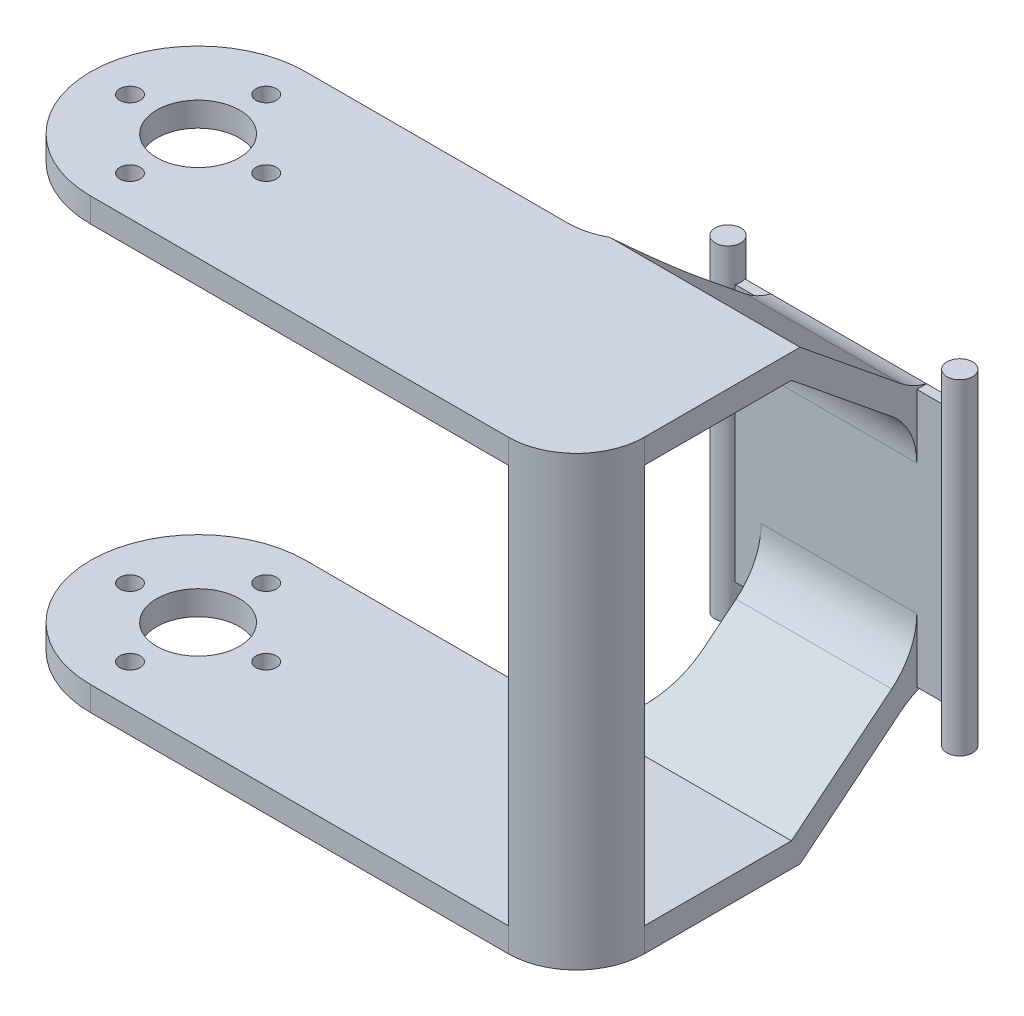
SolidWorks part; units mm, degrees
ref_plane "Front Plane" through (0, 0, 0) normal (0, 0, 1) x (1, 0, 0)
ref_plane "Top Plane" through (0, 0, 0) normal (0, 1, 0) x (1, 0, 0)
ref_plane "Right Plane" through (0, 0, 0) normal (1, 0, 0) x (0, 0, -1)
sketch "Sketch1" plane through (0, 0, 0) normal (0, 1, 0) x (1, 0, 0)
  line L1 (11.915, 0.5) -> (-11.915, 0.5)
  line L2 (11.915, 0.5) -> (11.915, -0.5)
  line L3 (11.915, -0.5) -> (-11.915, -0.5)
  line L4 (-11.915, 0.5) -> (-11.915, -0.5)
  line L5 (11.915, 0.5) -> (-11.915, -0.5) construction
  line L6 (11.915, -0.5) -> (-11.915, 0.5) construction
  point P0 (0, 0)
  dimension "D1" = 23.83
  dimension "D3" = 1
extrude "Boss-Extrude1" add sketch "Sketch1" along normal blind 26.5
ref_plane "Plane1" through (0, 13.25, 0) normal (0, 1, 0) x (1, 0, 0)
sketch "Sketch2" plane through (0, 13.25, 0) normal (0, 1, 0) x (1, 0, 0)
  line L0 (11.915, -0.5) -> (11.915, 0.5) construction
  line L1 (-11.915, 0.5) -> (-11.915, -0.5) construction
  line L2 (11.915, -0.5) -> (11.915, 0.5) construction
  line L3 (-11.915, 0.5) -> (-11.915, -0.5) construction
  circle A0 centre (-11.915, 0) radius 1.325
  circle A1 centre (11.915, 0) radius 1.325
  dimension "D1" = 2.65
extrude "Boss-Extrude2" add sketch "Sketch2" along normal mid plane 33.5
sketch "Sketch3" plane through (0, 26.5, 0) normal (0, 1, 0) x (1, 0, 0)
  line L0 (-10.688, -0.5) -> (10.688, -0.5) construction
  line L1 (-7.5, -0.5) -> (7.5, -0.5)
  line L2 (-7.5, -0.5) -> (-7.5, -26.5)
  line L3 (-7.5, -26.5) -> (7.5, -26.5)
  line L4 (7.5, -0.5) -> (7.5, -26.5)
  line L5 (0, -1000) -> (0, 49000) construction
  line L6 (-7.5, -26.5) -> (-32.5, -26.5)
  line L7 (-7.5, -26.5) -> (-7.5, -3.5)
  line L8 (-7.5, -3.5) -> (-32.5, -3.5)
  line L9 (-32.5, -26.5) -> (-32.5, -3.5)
  line L11 (-4.5, -3.5) -> (4.5, -3.5)
  line L12 (4.5, -3.5) -> (4.5, -23.5)
  line L13 (-4.5, -23.5) -> (4.5, -23.5)
  line L14 (-10.5, -23.5) -> (-29.5, -23.5)
  line L16 (-10.5, -6.5) -> (-29.5, -6.5)
  line L18 (-29.5, -23.5) -> (-29.5, -6.5) construction
  line L19 (-10.5, -23.5) -> (-10.5, -6.5) construction
  line L20 (-4.5, -3.5) -> (-4.5, -23.5) construction
  line L21 (-4.5, -3.5) -> (-4.5, -6.5)
  line L22 (-4.5, -6.5) -> (-10.5, -6.5)
  line L23 (-4.5, -23.5) -> (-10.5, -23.5)
  line L24 (-18.5, -6.5) -> (-18.5, -23.5)
  circle A0 centre (-32.5, -15) radius 11.5
  circle A1 centre (-32.5, -15) radius 4.25
  circle A2 centre (-32.5, -15) radius 7 construction
  circle A3 centre (-32.5, -8) radius 1.05
  circle A4 centre (-25.5, -15) radius 1.05
  circle A5 centre (-32.5, -22) radius 1.05
  circle A6 centre (-39.5, -15) radius 1.05
  point P10 (0, -0.5)
  line M14 (-10.688, -0.5) -> (10.688, -0.5)
  dimension "D5" = 8.5
  dimension "D6" = 14
  dimension "D7" = 2.1
  dimension "D1" = 15
  dimension "D2" = 26
  dimension "D3" = 23
  dimension "D4" = 25
  dimension "D9" = 14
  dimension "D8" = 3
extrude "Boss-Extrude3" [suppressed] add sketch "Sketch3" against normal up to surface (18.5 mm away) contours L4 L2 L3 M14 | A0 L6 L2 L8 | A5 L9 A0 A3 A1 A4 | A5 L9 A1 A3 A0 A6 | A0 L16 L22 L2 L8 | A0 L6 L2 L23 L14
sketch "Sketch4" plane through (0, 0, 0) normal (1, 0, 0) x (0, 0, -1)
  line L0 (-0.5, 26.5) -> (-12.5, 36.25)
  line L1 (-12.5, 36.25) -> (-35.5, 36.25)
  line L2 (-35.5, 36.25) -> (-35.5, 33.75)
  line L3 (-35.5, 33.75) -> (-13.3876, 33.75)
  line L4 (-13.3876, 33.75) -> (-0.5, 23.2788)
  line L5 (-0.5, 26.5) -> (-0.5, 0) construction
  line L6 (-0.5, 26.5) -> (-0.5, 0)
  line L7 (-0.5, 0) -> (-12.5, -9.75)
  line L8 (-12.5, -9.75) -> (-35.5, -9.75)
  line L9 (-35.5, -9.75) -> (-35.5, -7.25)
  line L10 (-35.5, -7.25) -> (-13.3876, -7.25)
  line L11 (-13.3876, -7.25) -> (-0.5, 3.2212)
  line L12 (-1000.5, 13.25) -> (48999.5, 13.25) construction
  line L13 (-35.5, 33.75) -> (-35.5, -7.25) construction
  point P3 (-35.5, 13.25)
  point P20 (-0.5, 13.25)
  dimension "D1" = 2.5
  dimension "D2" = 41
  dimension "D3" = 23
  dimension "D4" = 2.5
  dimension "D5" = 35
  dimension "D6" = 2.5
extrude "Boss-Extrude4" add sketch "Sketch4" along normal mid plane 16 contours L6 L0 L1 L2 L3 L4 | L11 L10 L9 L8 L7 L6
sketch "Sketch5" plane through (-8, 0, 0) normal (-1, 0, 0) x (0, 0, 1)
  line L1 (35.5, 36.25) -> (13.3876, 36.25)
  line L2 (35.5, 36.25) -> (35.5, 33.75)
  line L3 (35.5, 33.75) -> (13.3876, 33.75)
  line L4 (13.3876, 36.25) -> (13.3876, 33.75)
  line L5 (35.5, -9.75) -> (13.3876, -9.75)
  line L6 (35.5, -9.75) -> (35.5, -7.25)
  line L7 (35.5, -7.25) -> (13.3876, -7.25)
  line L8 (13.3876, -9.75) -> (13.3876, -7.25)
extrude "Boss-Extrude5" add sketch "Sketch5" along normal blind 45
sketch "Sketch6" plane through (0, 36.25, 0) normal (0, 1, 0) x (1, 0, 0)
  line L0 (-41.9438, -13.3876) -> (-41.9438, -35.5) construction
  line L1 (-53, -13.3876) -> (-8, -13.3876) construction
  line L2 (8, -35.5) -> (-53, -35.5) construction
  line L3 (-53, -24.4438) -> (8, -24.4438) construction
  line L4 (-53, -35.5) -> (-53, -13.3876) construction
  line L5 (8, -12.5) -> (8, -35.5) construction
  line L6 (-41.9438, -13.3876) -> (-53, -13.3876)
  line L7 (-53, -13.3876) -> (-53, -35.5)
  line L8 (-53, -35.5) -> (-41.9438, -35.5)
  circle A0 centre (-41.9438, -24.4438) radius 11.0562
  circle A1 centre (-41.9438, -24.4438) radius 4.25
  circle A2 centre (-41.9438, -24.4438) radius 7 construction
  circle A3 centre (-41.9438, -17.4438) radius 1.05
  circle A4 centre (-34.9438, -24.4438) radius 1.05
  circle A5 centre (-41.9438, -31.4438) radius 1.05
  circle A6 centre (-48.9438, -24.4438) radius 1.05
  point P12 (-41.9438, -24.4438)
  line M9 (-8, -13.3876) -> (-53, -13.3876)
  line M10 (-53, -13.3876) -> (-53, -35.5)
  line M11 (-53, -35.5) -> (8, -35.5)
  dimension "D1" = 8.5
  dimension "D2" = 14
  dimension "D3" = 2.1
extrude "Cut-Extrude1" cut sketch "Sketch6" against normal through all contours A1 | A6 | A3 | A4 | A5 | A0 M9 M10 | A0 L7 M11
fillet "Fillet1" radius 7 4 edges at (-8, -8.5, 13.3876) (-8, 35, 13.3876) (8, -8.5, 35.5) (8, 35, 35.5)
fillet "Fillet2" radius 7 2 edges at (0, 3.2212, 0.5) (0, 23.2788, 0.5)
fillet "Fillet3" radius 7 2 edges at (0, 26.5, 0.5) (0, 0, 0.5)
sketch "Sketch8" plane through (0, -7.25, 0) normal (0, 1, 0) x (1, 0, 0)
  line L0 (-41.9438, -13.3876) -> (-15, -13.3876) construction
  line L1 (-41.9438, -13.3876) -> (-15, -13.3876)
  line L2 (8, -28.5) -> (5, -28.5)
  line L3 (1, -35.5) -> (1, -32.5)
  arc A0 (-15, -13.3876) -> (-8, -6.3876) centre (-15, -6.3876) ccw construction
  arc A1 (1, -35.5) -> (8, -28.5) centre (1, -28.5) ccw construction
  arc A2 (-15, -13.3876) -> (-8, -6.3876) centre (-15, -6.3876) ccw
  arc A3 (1, -35.5) -> (8, -28.5) centre (1, -28.5) ccw
  circle A4 centre (-1.5277, -25.9723) radius 7
  arc M10 (1, -35.5) -> (8, -28.5) centre (1, -28.5) ccw
  dimension "D1" = 3
extrude "Boss-Extrude6" add sketch "Sketch8" along normal up to surface (41 mm away) contours A4 L3 L2 M10 up to face at (-41.9438, 33.75, 28.6938)
equation "\"D4@Sketch4\"=\"D1@Sketch4\""
equation "\"D6@Sketch4\"=\"D1@Sketch4\""
